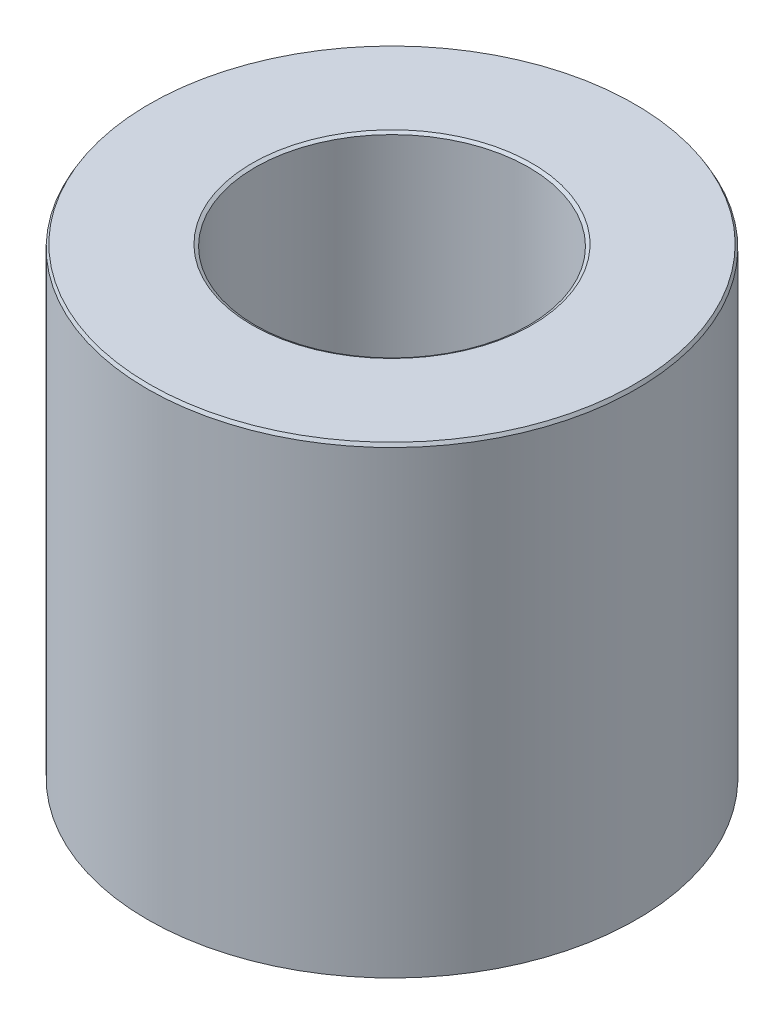
SolidWorks part; units mm, degrees
ref_plane "Front Plane" through (0, 0, 0) normal (0, 0, 1) x (1, 0, 0)
ref_plane "Top Plane" through (0, 0, 0) normal (0, 1, 0) x (1, 0, 0)
ref_plane "Right Plane" through (0, 0, 0) normal (1, 0, 0) x (0, 0, -1)
sketch "Sketch1" plane through (0, 0, 0) normal (0, 1, 0) x (1, 0, 0)
  circle A0 centre (0, 0) radius 57.5
  dimension "SLEEVE_OD" = 115
extrude "Boss-Extrude1" add sketch "Sketch1" along normal blind 109.2315
sketch "Sketch2" plane through (0, 0, 0) normal (0, 1, 0) x (1, 0, 0)
  circle A0 centre (0, 0) radius 32.1698
  dimension "BORE_D" = 64.3395
extrude "Cut-Extrude1" cut sketch "Sketch2" along normal through all
chamfer "Chamfer1" distance 0.7651 angle 30 4 edges at (0, 109.2315, 32.1698) (0, 0, 32.1698) (0, 0, 57.5) (0, 109.2315, 57.5) first distance on face at (0, 109.2315, 32.1698) first distance on face at (0, 0, 32.1698) first distance on face at (0, 109.2315, 57.5)
